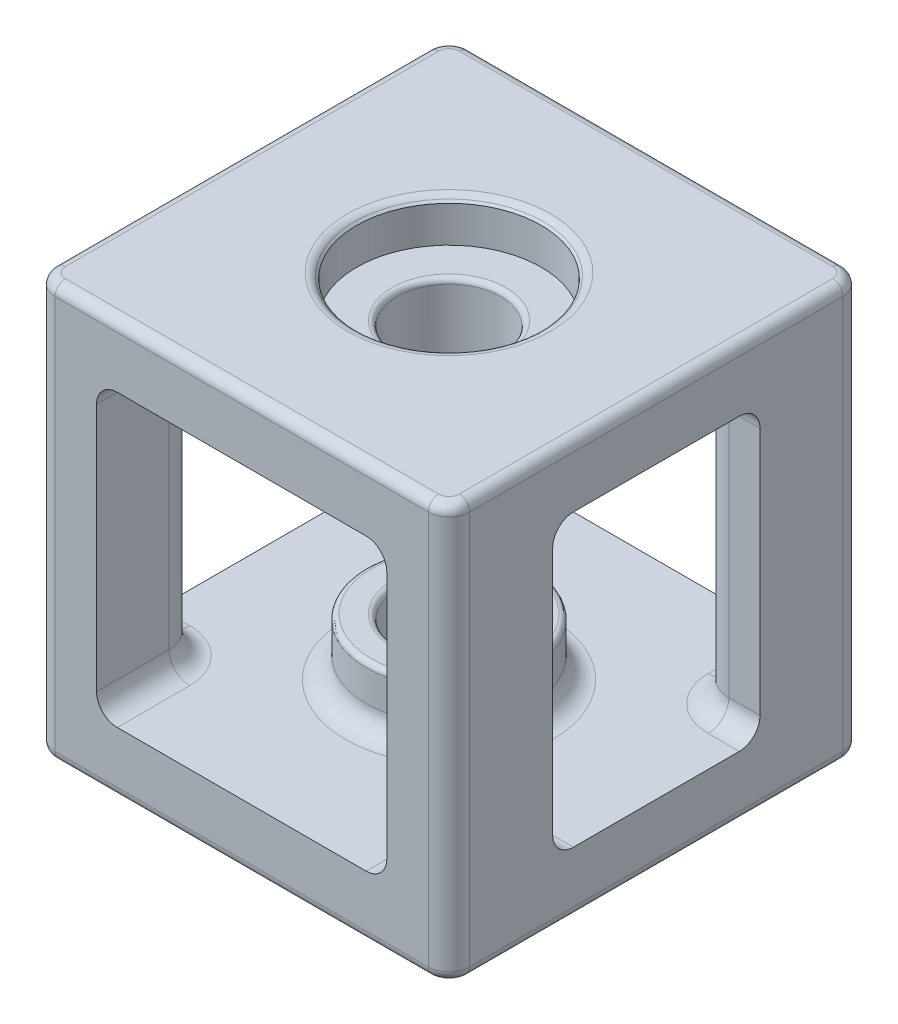
SolidWorks part; units mm, degrees
ref_plane "Front Plane" through (0, 0, 0) normal (0, 0, 1) x (1, 0, 0)
ref_plane "Top Plane" through (0, 0, 0) normal (0, 1, 0) x (1, 0, 0)
ref_plane "Right Plane" through (0, 0, 0) normal (1, 0, 0) x (0, 0, -1)
sketch "Sketch1" plane through (0, 0, 0) normal (0, 1, 0) x (1, 0, 0)
  line L0 (10, 5) -> (10, 10)
  line L1 (-10, 10) -> (10, 10)
  line L2 (-10, 10) -> (-10, -10)
  line L3 (-10, -10) -> (10, -10)
  line L4 (10, 10) -> (10, -10)
  line L5 (-10, 10) -> (10, -10) construction
  line L6 (-10, -10) -> (10, 10) construction
  line L7 (-7, 5) -> (-10, 5)
  line L8 (-7, 5) -> (-7, 10)
  line L9 (-7, 10) -> (-10, 10)
  line L10 (-10, 5) -> (-10, 10)
  line L11 (-7, 5) -> (-10, 10) construction
  line L12 (-7, 10) -> (-10, 5) construction
  line L13 (10, 5) -> (7, 5)
  line L14 (7, 5) -> (7, 10)
  line L15 (10, 10) -> (7, 10)
  line L16 (10, -10) -> (10, -5)
  line L17 (10, -10) -> (7, -10)
  line L18 (7, -10) -> (7, -5)
  line L19 (10, -5) -> (7, -5)
  line L20 (-7, -10) -> (-7, -5)
  line L21 (-7, -10) -> (-10, -10)
  line L22 (-10, -10) -> (-10, -5)
  line L23 (-7, -5) -> (-10, -5)
  circle A0 centre (0, 0) radius 4
  point P0 (0, 0)
  point P8 (-8.5, 7.5)
  dimension "D3" = 8
  dimension "D1" = 20
  dimension "D2" = 20
  dimension "D4" = 3
  dimension "D5" = 5
  dimension "D6" = 2
  dimension "D7" = 2
extrude "Boss-Extrude1" add sketch "Sketch1" along normal blind 3 contours L2 L3 L4 L1
extrude "Boss-Extrude2" add sketch "Sketch1<3>" along normal blind 5.75 contours A0
sketch "Sketch1<3>" plane through (0, 0, 0) normal (0, 1, 0) x (1, 0, 0) same geometry as "Sketch1"
sketch "Sketch2" plane through (0, 5.75, 0) normal (0, 1, 0) x (1, 0, 0)
  circle A0 centre (0, 0) radius 2.5
  dimension "D1" = 5
extrude "Cut-Extrude1" cut sketch "Sketch2" against normal up to surface (5.75 mm away) up to face at (0, 0, 0)
ref_plane "Plane1" through (0, 10, 0) normal (0, 1, 0) x (1, 0, 0)
extrude "Boss-Extrude3" add sketch "Sketch1<4>" along normal blind 20 contours L9 L8 L7 L10 | L13 L14 L15 L0 | L19 L18 L17 L16 | L23 L22 L21 L20
sketch "Sketch1<4>" plane through (0, 0, 0) normal (0, 1, 0) x (1, 0, 0) same geometry as "Sketch1"
mirror "Mirror2" about plane through (0, 10, 0) normal (0, 1, 0) of "Cut-Extrude1", "Boss-Extrude1", "Boss-Extrude2"
fillet "Fillet1" radius 1 4 edges at (-10, 10, -10) (10, 10, -10) (10, 10, 10) (-10, 10, 10)
fillet "Fillet2" radius 1.5 4 edges at (-7, 10, 5) (7, 10, 5) (7, 10, -5) (-7, 10, -5)
fillet "Fillet5" radius 1 26 edges at (-9.25, 3, 5) (-7.4393, 3, 5.4393) (-9.25, 3, -5) (-7.4393, 3, -5.4393) (7, 3, 8.25) (7.4393, 3, 5.4393) (9.25, 3, -5) (7.4393, 3, -5.4393) (0, 3, -4) (-7, 3, 8.25) (-7, 3, -8.25) (9.25, 3, 5) (7, 3, -8.25) (9.25, 17, 5) (7.4393, 17, 5.4393) (-9.25, 17, 5) (-7.4393, 17, 5.4393) (-7, 17, -8.25) (-7.4393, 17, -5.4393) (7, 17, -8.25) (7.4393, 17, -5.4393) (7, 17, 8.25) (-7, 17, 8.25) (-9.25, 17, -5) (0, 17, 4) (9.25, 17, -5)
sketch "Sketch5" plane through (0, 20, 0) normal (0, 1, 0) x (1, 0, 0)
  circle A0 centre (0, 0) radius 4.45
  dimension "D1" = 8.9
extrude "Cut-Extrude2" cut sketch "Sketch5" against normal blind 2
chamfer "Chamfer1" distance 0.25 angle 45 1 edges at (0, 20, 4.45)
fillet "Fillet6" radius 0.5 18 edges at (0, 0, -2.5) (-9.7071, 0, 9.7071) (0, 0, 10) (9.7071, 0, 9.7071) (10, 0, 0) (9.7071, 0, -9.7071) (0, 0, -10) (-9.7071, 0, -9.7071) (-10, 0, 0) (9.7071, 20, -9.7071) (10, 20, 0) (9.7071, 20, 9.7071) (0, 20, 10) (-9.7071, 20, 9.7071) (-10, 20, 0) (-9.7071, 20, -9.7071) (0, 20, -10) (0, 20, 4.7)
fillet "Fillet7" radius 0.25 5 edges at (0, 5.75, 4) (0, 14.25, 4) (0, 14.25, 2.5) (0, 5.75, 2.5) (0, 18, 2.5)
